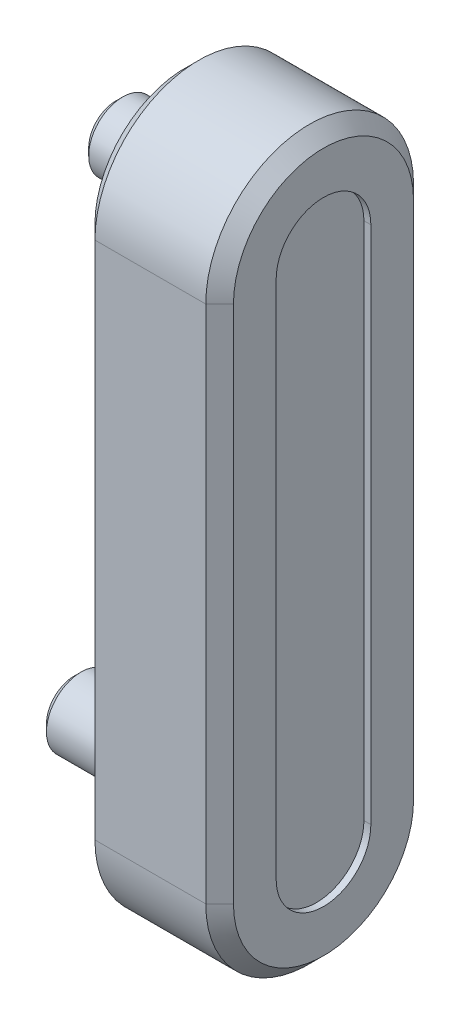
SolidWorks part; units mm, degrees
ref_plane "前视基准面" through (0, 0, 0) normal (0, 0, 1) x (1, 0, 0)
ref_plane "上视基准面" through (0, 0, 0) normal (0, 1, 0) x (1, 0, 0)
ref_plane "右视基准面" through (0, 0, 0) normal (1, 0, 0) x (0, 0, -1)
other "Configuration Table"
sketch "草图1" plane through (0, 0, 0) normal (1, 0, 0) x (0, 0, -1)
  circle A0 centre (0, 0) radius 4.9
  dimension "D1" = 9.8
extrude "凸台-拉伸1" add sketch "草图1" along normal blind 10
sketch "草图2" plane through (10, 0, 0) normal (1, 0, 0) x (0, 0, -1)
  line L0 (0, 0) -> (0, -75) construction
  line L1 (15, 0) -> (15, -75)
  line L2 (-15, 0) -> (-15, -75)
  arc A1 (15, 0) -> (-15, 0) centre (0, 0) ccw
  arc A2 (-15, -75) -> (15, -75) centre (0, -75) ccw
  point P3 (0, -37.5)
  dimension "D1" = 15
  dimension "D2" = 75
extrude "凸台-拉伸2" add sketch "草图2" along normal blind 20
sketch "草图3" plane through (10, 0, 0) normal (-1, 0, 0) x (0, 0, 1)
  circle A0 centre (0, -75) radius 5
extrude "凸台-拉伸3" add sketch "草图3" along normal blind 16
chamfer "倒角1" distance 2 angle 45 8 edges at (10, -37.5, -15) (10, 15, 0) (10, -90, 0) (10, -37.5, 15) (30, -37.5, -15) (30, 15, 0) (30, -90, 0) (30, -37.5, 15)
sketch "草图4" plane through (30, 0, 0) normal (1, 0, 0) x (0, 0, -1)
  line L0 (0, 0) -> (0, -75) construction
  line L1 (6.8356, 0) -> (6.8356, -75)
  line L2 (-6.8356, 0) -> (-6.8356, -75)
  arc A0 (6.8356, 0) -> (-6.8356, 0) centre (0, 0) ccw
  arc A1 (-6.8356, -75) -> (6.8356, -75) centre (0, -75) ccw
  point P4 (0, -37.5)
extrude "切除-拉伸1" cut sketch "草图4" against normal blind 1
sketch "草图5" plane through (10, 0, 0) normal (-1, 0, 0) x (0, 0, 1)
  circle A0 centre (0, -75) radius 10
extrude "凸台-拉伸4" add sketch "草图5" along normal blind 1
chamfer "倒角2" distance 1 angle 45 1 edges at (9, -75, 10)
chamfer "倒角3" distance 1 angle 45 2 edges at (0, 0, -4.9) (-6, -75, 5)
